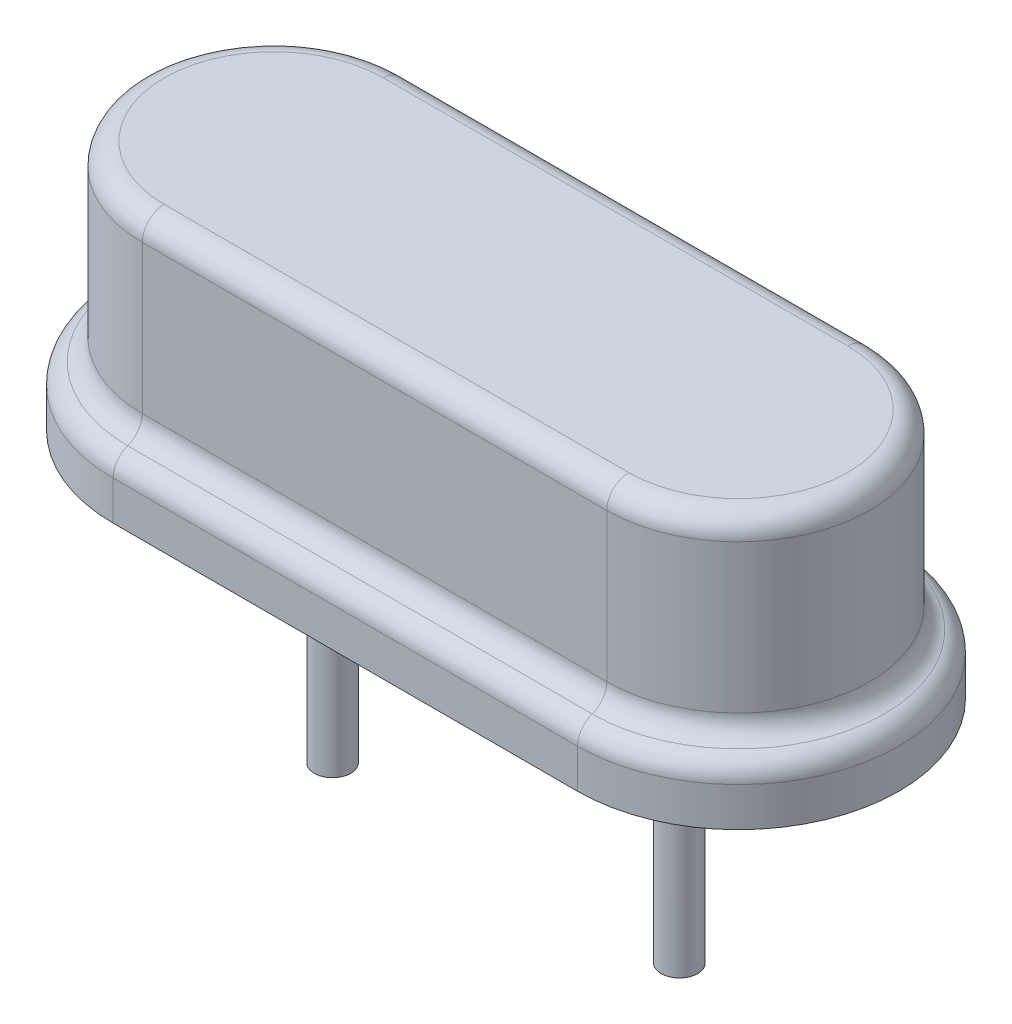
SolidWorks part; units mm, degrees
ref_plane "Alzado" through (0, 0, 0) normal (0, 0, 1) x (1, 0, 0)
ref_plane "Planta" through (0, 0, 0) normal (0, 1, 0) x (1, 0, 0)
ref_plane "Vista lateral" through (0, 0, 0) normal (1, 0, 0) x (0, 0, -1)
sketch "Croquis1" plane through (0, 0, 0) normal (0, 1, 0) x (1, 0, 0)
  line L0 (0, 0) -> (6.36, 0)
  line L1 (6.36, 4.4) -> (0, 4.4)
  line L2 (0, 0.4) -> (6.36, 0.4)
  line L3 (6.36, 4) -> (0, 4)
  arc A0 (0, 4.4) -> (0, 0) centre (0, 2.2) ccw
  arc A1 (6.36, 4.4) -> (6.36, 0) centre (6.36, 2.2) cw
  arc A2 (6.36, 4) -> (6.36, 0.4) centre (6.36, 2.2) cw
  arc A3 (0, 4) -> (0, 0.4) centre (0, 2.2) ccw
  point P7 (-2.2, 2.2)
  point P8 (8.56, 2.2)
  dimension "D1" = 2.2
  dimension "D2" = 10.76
  dimension "D3" = 0.4
extrude "Saliente-Extruir1" add sketch "Croquis1" along normal blind 3.43 contours L2 A2 L3 A3
extrude "Saliente-Extruir2" add sketch "Croquis1<3>" along normal blind 0.8
sketch "Croquis1<3>" plane through (0, 0, 0) normal (0, 1, 0) x (1, 0, 0) same geometry as "Croquis1"
fillet "Redondeo2" radius 0.3 8 edges at (3.18, 3.43, -0.4) (8.16, 3.43, -2.2) (3.18, 3.43, -4) (-1.8, 3.43, -2.2) (-1.8, 0.8, -2.2) (3.18, 0.8, -4) (8.16, 0.8, -2.2) (3.18, 0.8, -0.4)
fillet "Redondeo5" radius 0.3 4 edges at (-2.2, 0.8, -2.2) (3.18, 0.8, -4.4) (8.56, 0.8, -2.2) (3.18, 0.8, 0)
sketch "Croquis2" plane through (0, 0, 0) normal (0, -1, 0) x (1, 0, 0)
  line L0 (0.805, -2.2) -> (5.555, -2.2) construction
  line L1 (0, 0) -> (6.36, 0) construction
  circle A0 centre (0.805, -2.2) radius 0.25
  circle A1 centre (5.555, -2.2) radius 0.25
  arc A2 (6.36, -4.4) -> (6.36, 0) centre (6.36, -2.2) ccw construction
  point P4 (3.18, -2.2)
  point P5 (3.18, 0)
  point P6 (8.56, -2.2)
  dimension "D1" = 0.5
  dimension "D2" = 4.75
extrude "Saliente-Extruir3" add sketch "Croquis2" along normal blind 3.54
